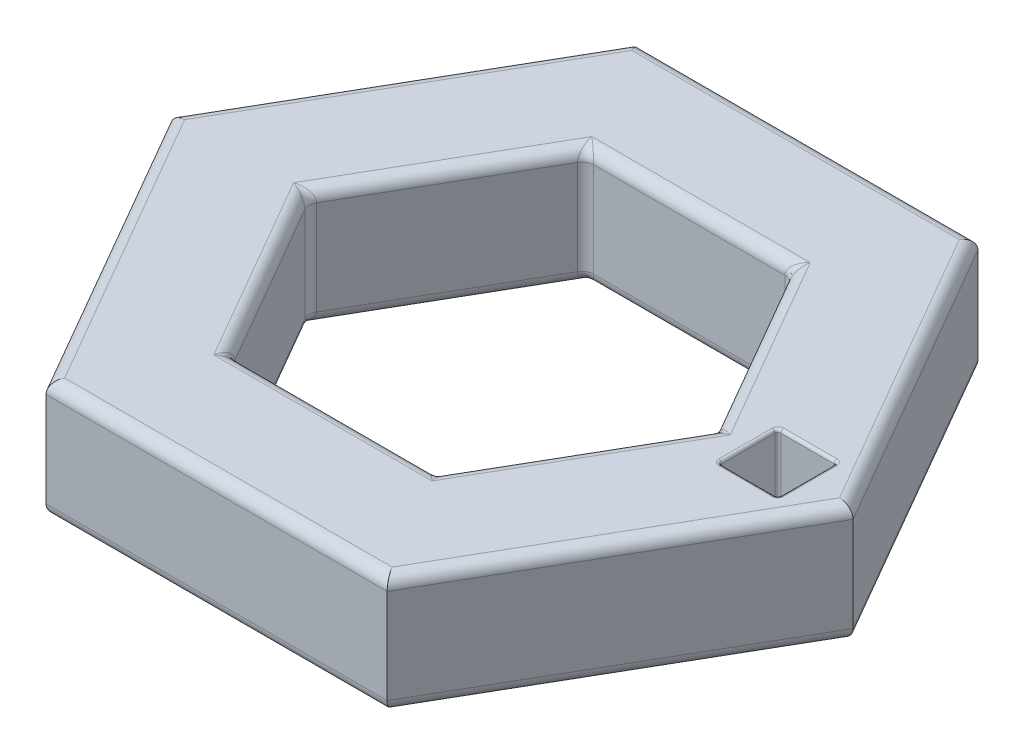
SolidWorks part; units mm, degrees
ref_plane "Front" through (0, 0, 0) normal (0, 0, 1) x (1, 0, 0)
ref_plane "Top" through (0, 0, 0) normal (0, 1, 0) x (1, 0, 0)
ref_plane "Right" through (0, 0, 0) normal (1, 0, 0) x (0, 0, -1)
ref_plane "Plane1" through (0, -10, 0) normal (0, -1, 0) x (1, 0, 0)
sketch "Sketch1" plane through (0, -10, 0) normal (0, -1, 0) x (1, 0, 0)
  line L0 (14.4338, -25) -> (28.8675, 0)
  line L1 (28.8675, 0) -> (14.4338, 25)
  line L2 (14.4338, 25) -> (-14.4338, 25)
  line L3 (-14.4338, 25) -> (-28.8675, 0)
  line L4 (-28.8675, 0) -> (-14.4338, -25)
  line L5 (-14.4338, -25) -> (14.4338, -25)
  line L6 (-8.6603, -15) -> (8.6603, -15)
  line L7 (8.6603, -15) -> (17.3205, 0)
  line L8 (17.3205, 0) -> (8.6603, 15)
  line L9 (8.6603, 15) -> (-8.6603, 15)
  line L10 (-8.6603, 15) -> (-17.3205, 0)
  line L11 (-17.3205, 0) -> (-8.6603, -15)
  circle A0 centre (0, 0) radius 25 construction
  dimension "D1" = 50
  dimension "D2" = 10
extrude "Boss-Extrude1" add sketch "Sketch1" against normal blind 10
fillet "Fillet1" radius 1 24 edges at (0, -10, -15) (12.9904, -10, -7.5) (12.9904, -10, 7.5) (0, -10, 15) (-12.9904, -10, 7.5) (-12.9904, -10, -7.5) (-21.6506, -10, -12.5) (-21.6506, -10, 12.5) (0, -10, 25) (21.6506, -10, 12.5) (21.6506, -10, -12.5) (0, -10, -25) (0, 0, 15) (12.9904, 0, 7.5) (12.9904, 0, -7.5) (0, 0, -15) (-12.9904, 0, -7.5) (-12.9904, 0, 7.5) (21.6506, 0, -12.5) (21.6506, 0, 12.5) (0, 0, 25) (-21.6506, 0, 12.5) (-21.6506, 0, -12.5) (0, 0, -25)
fillet "Fillet2" radius 1 18 edges at (-8.8294, -0.2929, 15.2929) (-8.8294, -9.7071, 15.2929) (8.8294, -0.2929, 15.2929) (8.8294, -9.7071, 15.2929) (17.6587, -0.2929, 0) (17.6587, -9.7071, 0) (8.8294, -0.2929, -15.2929) (8.8294, -9.7071, -15.2929) (-8.8294, -0.2929, -15.2929) (-8.8294, -9.7071, -15.2929) (-17.6587, -0.2929, 0) (-17.6587, -9.7071, 0) (-8.6603, -5, 15) (8.6603, -5, 15) (17.3205, -5, 0) (8.6603, -5, -15) (-8.6603, -5, -15) (-17.3205, -5, 0)
sketch "Sketch2" plane through (0, 0, 0) normal (0, 1, 0) x (-1, 0, 0)
  line L0 (-20, 2.5) -> (-25, 2.5)
  line L1 (-25, 2.5) -> (-25, -2.5)
  line L2 (-25, -2.5) -> (-20, -2.5)
  line L3 (-20, -2.5) -> (-20, 2.5)
  line L4 (-20, -2.5) -> (-25, 2.5) construction
  line L5 (-25, -2.5) -> (-20, 2.5) construction
  point P8 (-22.5, 0)
  dimension "D1" = 5
  dimension "D2" = 22.5
extrude "Cut-Extrude1" cut sketch "Sketch2" against normal through all
fillet "Fillet3" radius 0.25 12 edges at (25, 0, 0) (22.5, 0, -2.5) (22.5, 0, 2.5) (20, 0, 0) (25, -10, 0) (22.5, -10, -2.5) (22.5, -10, 2.5) (20, -10, 0) (20, -5, 2.5) (20, -5, -2.5) (25, -5, -2.5) (25, -5, 2.5) tangent propagation no
